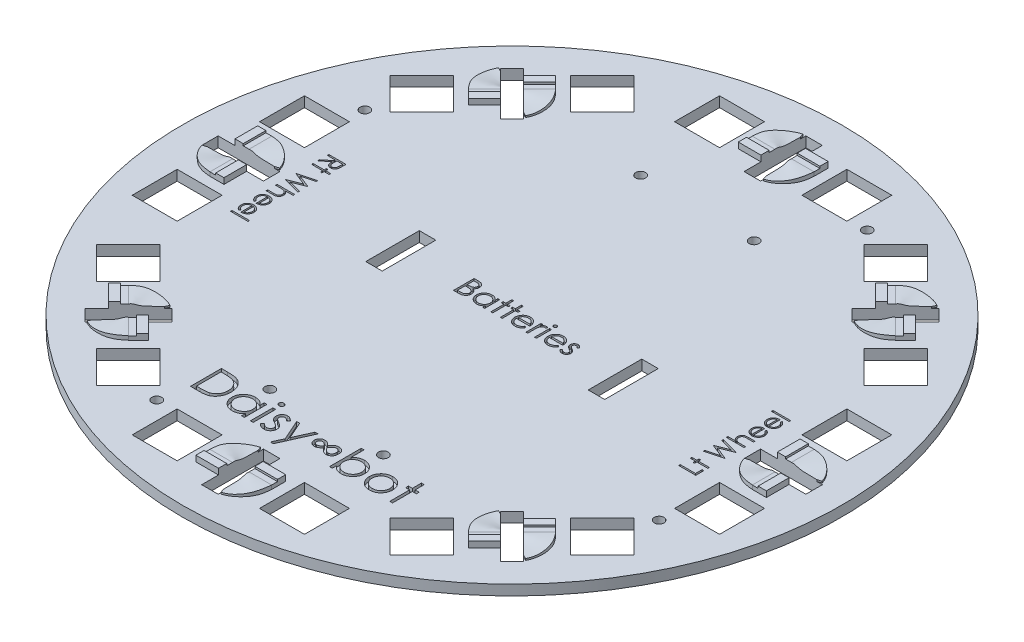
SolidWorks part; units mm, degrees
ref_plane "Front" through (0, 0, 0) normal (0, 0, 1) x (1, 0, 0)
ref_plane "Top" through (0, 0, 0) normal (0, 1, 0) x (1, 0, 0)
ref_plane "Right" through (0, 0, 0) normal (1, 0, 0) x (0, 0, -1)
sketch "Sketch1" plane through (0, 0, 0) normal (0, 1, 0) x (1, 0, 0)
  circle A0 centre (0, 0) radius 101.6
  dimension "D1" = 203.2
extrude "Boss-Extrude1" add sketch "Sketch1" along normal blind 3.175 contours A0
sketch "Sketch2" plane through (0, 3.175, 0) normal (0, 1, 0) x (1, 0, 0)
  line L1 (-2.54, -93.1333) -> (2.54, -93.1333)
  line L2 (-2.54, -93.1333) -> (-2.54, -74.0833)
  line L3 (-2.54, -74.0833) -> (2.54, -74.0833)
  line L4 (2.54, -93.1333) -> (2.54, -74.0833)
  circle A0 centre (0, 0) radius 101.6 construction
  point P4 (0, -74.0833)
  dimension "D1" = 5.08
  dimension "D2" = 19.05
  dimension "D3" = 93.1333
extrude "Cut-Extrude1" cut sketch "Sketch2" against normal up to next and the other way through all contours L1 L4 L3 L2
sketch "Sketch4" plane through (0, 3.175, 0) normal (0, 1, 0) x (1, 0, 0)
  line L0 (0, -83.6083) -> (-2.9434, -74.5495) construction
  line L1 (-2.9434, -74.5495) -> (0, -83.6083) construction
  line L2 (0, -83.6083) -> (-5.5987, -75.9025) construction
  line L3 (0, -83.6083) -> (-7.7059, -78.0097) construction
  line L4 (0, -83.6083) -> (-9.0588, -80.665) construction
  line L5 (0, -83.6083) -> (-9.525, -83.6083) construction
  line L9 (2.54, -74.0833) -> (-2.54, -74.0833) construction
  line L10 (2.54, -74.0833) -> (2.54, -93.1333) construction
  line L11 (-2.54, -74.0833) -> (-2.54, -93.1333) construction
  line L12 (2.54, -93.1333) -> (-2.54, -93.1333) construction
  circle A0 centre (0, -83.6083) radius 9.525 construction
  point P16 (0, -74.0833)
  point P19 (2.54, -83.6083)
  dimension "D1" = 18
  dimension "D2" = 18
  dimension "D3" = 18
  dimension "D4" = 18
  dimension "D5" = 18
ref_plane "Plane1" through (-24.5719, 0, 7.9839) normal (0.9511, 0, -0.309) x (-0.309, 0, -0.9511)
ref_plane "Plane2" through (-39.7581, 0, 28.886) normal (0.809, 0, -0.5878) x (-0.5878, 0, -0.809)
ref_plane "Plane3" through (-39.7581, 0, 54.7224) normal (0.5878, 0, -0.809) x (-0.809, 0, -0.5878)
ref_plane "Plane4" through (-24.5719, 0, 75.6245) normal (0.309, 0, -0.9511) x (-0.9511, 0, -0.309)
ref_plane "Plane5" through (0, 0, 83.6083) normal (0, 0, -1) x (-1, 0, 0)
sketch "Sketch5" plane through (-24.5719, 0, 7.9839) normal (0.9511, 0, -0.309) x (-0.309, 0, -0.9511)
  line L0 (-69.6725, 3.175) -> (-87.7902, 3.175) construction
  line L1 (-71.2966, 3.175) -> (-69.9913, 3.175)
  line L2 (-71.2966, 3.175) -> (-71.2966, 3.683)
  line L3 (-71.2966, 3.683) -> (-69.9913, 3.683)
  line L4 (-69.9913, 3.175) -> (-69.9913, 3.683)
  dimension "D2" = 0.508
sketch "Sketch6" plane through (-39.7581, 0, 28.886) normal (0.809, 0, -0.5878) x (-0.5878, 0, -0.809)
  line L0 (-58.4417, 3.175) -> (-73.8535, 3.175) construction
  line L1 (-63.3193, 3.175) -> (-58.1156, 3.175)
  line L2 (-63.3193, 3.175) -> (-63.3193, 3.775)
  line L3 (-63.3193, 3.775) -> (-58.1156, 3.775)
  line L4 (-58.1156, 3.175) -> (-58.1156, 3.775)
  dimension "D2" = 0.6
sketch "Sketch7" plane through (-39.7581, 0, 54.7224) normal (0.5878, 0, -0.809) x (-0.809, 0, -0.5878)
  line L0 (-41.4902, 3.175) -> (-52.6875, 3.175) construction
  line L1 (-46.0041, 3.175) -> (-39.6188, 3.175)
  line L2 (-46.0041, 3.175) -> (-46.0041, 4.075)
  line L3 (-46.0041, 4.075) -> (-39.6188, 4.075)
  line L4 (-39.6188, 3.175) -> (-39.6188, 4.075)
  dimension "D2" = 0.9
sketch "Sketch10" plane through (-24.5719, 0, 75.6245) normal (0.309, 0, -0.9511) x (-0.9511, 0, -0.309)
  line L0 (-25.8364, 3.175) -> (-16.7776, 3.175) construction
  line L1 (-23.1657, 3.175) -> (-16.3114, 3.175)
  line L2 (-23.1657, 3.175) -> (-23.1657, 4.375)
  line L3 (-23.1657, 4.375) -> (-16.3114, 4.375)
  line L4 (-16.3114, 3.175) -> (-16.3114, 4.375)
  dimension "D3" = 1.2
sketch "Sketch11" plane through (0, 0, 83.6083) normal (0, 0, -1) x (-1, 0, 0)
  line L0 (0, 3.175) -> (9.525, 3.175) construction
  line L1 (2.54, 3.175) -> (9.525, 3.175)
  line L2 (2.54, 3.175) -> (2.54, 4.375)
  line L3 (2.54, 4.375) -> (9.525, 4.375)
  line L4 (9.525, 3.175) -> (9.525, 4.375)
  dimension "D3" = 1.2
loft "Loft1" add profiles "Sketch5", "Sketch6", "Sketch7", "Sketch10", "Sketch11" connector at (-2.54, 3.683, 75.791) connector at (-2.54, 3.775, 80.1123) connector at (-2.54, 4.075, 81.7629) connector at (-2.54, 4.375, 82.783) connector at (-2.54, 4.375, 83.6083)
sketch "Sketch13" plane through (-104.9799, 0, 83.6083) normal (0, 0, -1) x (-1, 0, 0)
  line L6 (-95.4549, 3.175) -> (-102.4399, 3.175)
  line L7 (-95.4549, 3.175) -> (-95.4549, 4.375)
  line L8 (-95.4549, 4.375) -> (-102.4399, 4.375)
  line L9 (-102.4399, 3.175) -> (-102.4399, 4.375)
extrude "Boss-Extrude4" add sketch "Sketch13" against normal blind 1.7907
sketch "Sketch25" plane through (0, 0, 85.399) normal (0, 0, 1) x (1, 0, 0)
  line L0 (-9.525, 4.375) -> (-2.54, 4.375) construction
  line L1 (-9.525, 3.175) -> (-2.54, 3.175)
  line L2 (-9.525, 3.175) -> (-9.525, 4.975)
  line L3 (-9.525, 4.975) -> (-2.54, 4.975)
  line L4 (-2.54, 3.175) -> (-2.54, 4.975)
  dimension "D1" = 0.6
extrude "Boss-Extrude5" add sketch "Sketch25" along normal blind 2.54
sketch "Sketch14" plane through (-2.54, 0, 0) normal (1, 0, 0) x (0, 0, -1)
  line L0 (-83.6083, 3.175) -> (-83.6083, 0) construction
  line L1 (-74.0833, 0) -> (-93.1333, 0) construction
ref_plane "Plane6" through (0, 0, 0) normal (1, 0, 0) x (0, 0, -1)
sketch "Sketch15" plane through (0, 0, 0) normal (1, 0, 0) x (0, 0, -1)
  line L0 (-83.6083, 0) -> (-83.6083, 3.175) construction
pattern_circular "CirPattern1" count 2 over 360 about axis through (0, 0, 83.6083) along (0, 1, 0) of "Loft1", "Boss-Extrude5", "Boss-Extrude4" reverse direction yes
ref_axis "Axis1" through (0, 50, 0) along (0, -1, 0)
pattern_circular "CirPattern5" count 8 over 360 about axis through (0, 50, 0) along (0, -1, 0) of "CirPattern1", "Cut-Extrude1"
sketch "Sketch18" plane through (0, 3.175, 0) normal (0, 1, 0) x (1, 0, 0)
  line L4 (0, -101.6) -> (0, 101.6) construction
  line L5 (0, -1.7463) -> (0, 1.7463) construction
  line L6 (-101.6, 0) -> (101.6, 0) construction
  circle A8 centre (0, 0) radius 101.6 construction
sketch "Sketch19" plane through (0, 3.175, 0) normal (0, 1, 0) x (1, 0, 0)
  line L0 (-32.0765, -77.4396) -> (0, 0) construction
  line L1 (0, -101.6) -> (0, 101.6) construction
  circle A1 centre (-32.0765, -77.4396) radius 1.5
  dimension "D1" = 83.82
  dimension "D4" = 3
  dimension "D5" = 22.5
extrude "Cut-Extrude2" cut sketch "Sketch19" against normal through all
pattern_circular "CirPattern7" count 4 over 360 about axis through (0, 50, 0) along (0, -1, 0) of "Cut-Extrude2"
sketch "Sketch23" plane through (0, 3.175, 0) normal (0, 1, 0) x (1, 0, 0)
  line L9 (-2.54, -87.939) -> (-2.54, -93.1333) construction
  line L10 (-26.5557, -76.6805) -> (-12.7, -76.6805)
  line L11 (-26.5557, -76.6805) -> (-26.5557, -90.5362)
  line L16 (-26.5557, -90.5362) -> (-12.7, -90.5362)
  line L17 (-12.7, -76.6805) -> (-12.7, -90.5362)
  line L19 (2.54, -74.0833) -> (2.54, -79.2776) construction
  line L20 (0, -50) -> (0, 50) construction
  line L21 (12.7, -76.6805) -> (12.7, -90.5362)
  line L22 (26.5557, -90.5362) -> (12.7, -90.5362)
  line L23 (26.5557, -76.6805) -> (26.5557, -90.5362)
  line L24 (26.5557, -76.6805) -> (12.7, -76.6805)
  point P8 (-2.54, -90.5362)
  point P9 (2.54, -76.6805)
  dimension "D2" = 10.16
extrude "Cut-Extrude6" cut sketch "Sketch23" against normal through all
pattern_circular "CirPattern8" count 8 over 360 about axis through (0, 50, 0) along (0, -1, 0) of "Cut-Extrude6"
sketch "Sketch16" plane through (0, 3.175, 0) normal (0, 1, 0) x (1, 0, 0)
  line L0 (2.54, -74.0833) -> (-2.54, -74.0833) construction
  line L1 (-16.4163, -2.4279) -> (16.4163, -2.4279) construction
  line L2 (0, -101.6) -> (0, 101.6) construction
  line L3 (-71.12, 15.3104) -> (-71.12, -15.3104) construction
  line L4 (-101.6, 0) -> (101.6, 0) construction
  line L5 (71.12, 15.3104) -> (71.12, -15.3104) construction
  line L6 (-31.75, -68.58) -> (31.75, -68.58) construction
  circle A1 centre (0, 0) radius 101.6 construction
  text T0 "Daisy∞bot\r\n" font "Century Gothic" height in points 36
  text T1 "Batteries"
  text T2 "Rt Wheel\r\n" font "Century Gothic" height in points 20
  text T3 "Lt Wheel" font "Century Gothic" height in points 20
  point P4 (-71.12, 0)
  point P7 (0, -68.58)
  point P10 (0, -2.4279)
  point P15 (71.12, 0)
  point P22 (0, 0)
  point P23 (5.8188, 7.285)
  point P24 (0, -47.135)
  dimension "D1" = 32.8326
  dimension "D2" = 30.6207
  dimension "D3" = 63.5
  dimension "D4" = 71.12
  dimension "D5" = 71.12
  dimension "D6" = 68.58
extrude "Cut-Extrude4" cut sketch "Sketch16" against normal blind 1.27
sketch "Sketch26" plane through (0, 3.175, 0) normal (0, 1, 0) x (1, 0, 0)
  line L0 (-101.6, 0) -> (101.6, 0) construction
  line L1 (-36.83, 8.255) -> (-31.75, 8.255)
  line L2 (-36.83, 8.255) -> (-36.83, -8.255)
  line L3 (-36.83, -8.255) -> (-31.75, -8.255)
  line L4 (-31.75, 8.255) -> (-31.75, -8.255)
  line L5 (0, -101.6) -> (0, 101.6) construction
  point P4 (-36.83, 0)
  dimension "D1" = 16.51
  dimension "D2" = 5.08
  dimension "D3" = 31.75
extrude "Cut-Extrude7" cut sketch "Sketch26" against normal through all
mirror "Mirror1" about plane through (0, 0, 0) normal (1, 0, 0) of "Cut-Extrude7"
sketch "Sketch27" plane through (0, 0, 0) normal (0, -1, 0) x (1, 0, 0)
  line L0 (0, 101.6) -> (0, -101.6) construction
  line L1 (-101.6, 0) -> (101.6, 0) construction
  circle A0 centre (-17.5, -57.15) radius 1.5
  circle A1 centre (-77.4396, -32.0765) radius 1.5 construction
  dimension "D1" = 17.5
  dimension "D2" = 57.15
extrude "Cut-Extrude8" cut sketch "Sketch27" against normal through all both and the other way through all
mirror "Mirror2" about plane through (0, 0, 0) normal (0, 0, 1) of "Cut-Extrude8"
mirror "Mirror3" about plane through (0, 0, 0) normal (1, 0, 0) of "Mirror2"
sketch "Sketch28" plane through (0, 0, 0) normal (0, -1, 0) x (1, 0, 0)
  line L0 (-21.8435, -50.8) -> (21.8435, -50.8) construction
  line L1 (0, 101.6) -> (0, -101.6) construction
  line L2 (-101.6, 0) -> (101.6, 0) construction
  line L3 (-19.568, 50.8) -> (19.568, 50.8) construction
  text T0 "Bk Caster"
  text T1 "Ft Caster"
  point P3 (0, 50.8)
  point P4 (0, -50.8)
  dimension "D1" = 50.8
  dimension "D2" = 50.8
extrude "Cut-Extrude9" cut sketch "Sketch28" against normal blind 1.27
